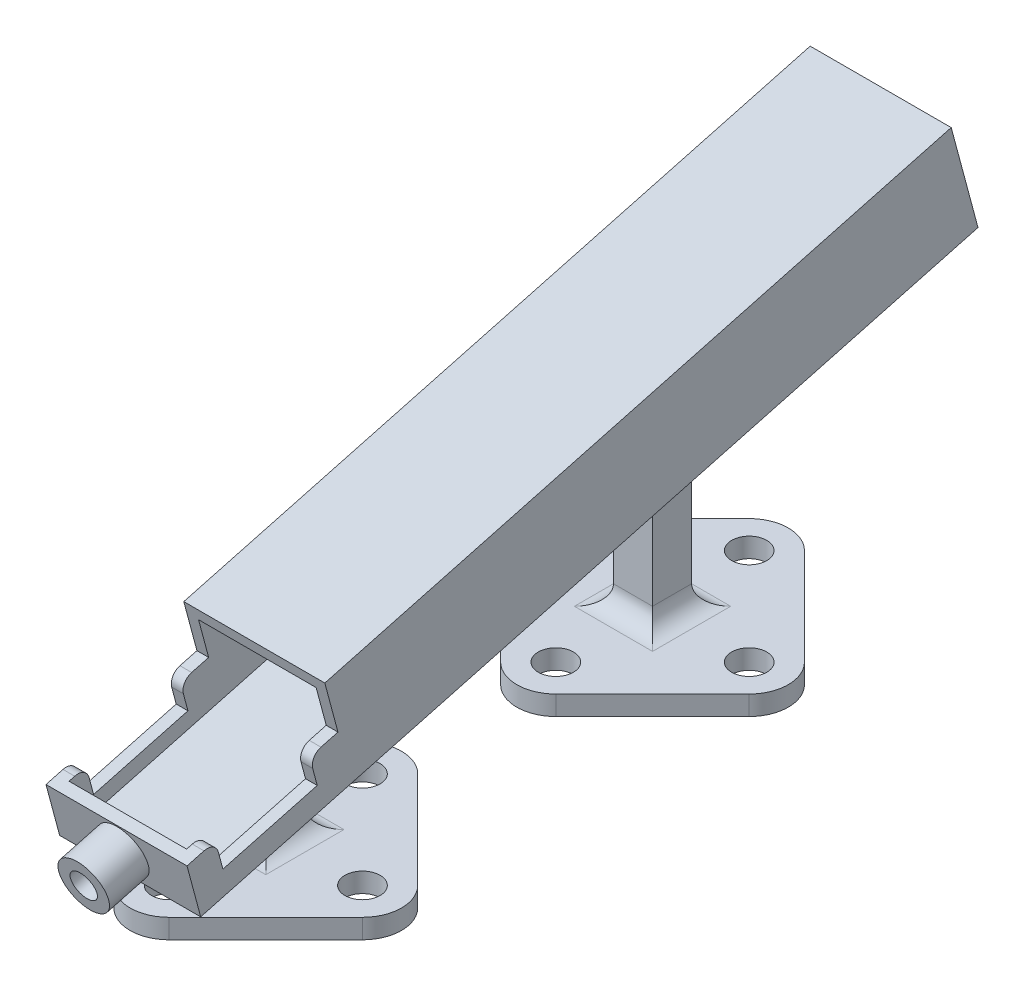
SolidWorks part; units mm, degrees
ref_plane "Front" through (0, 0, 0) normal (0, 0, 1) x (1, 0, 0)
ref_plane "Top" through (0, 0, 0) normal (0, 1, 0) x (1, 0, 0)
ref_plane "Right" through (0, 0, 0) normal (1, 0, 0) x (0, 0, -1)
ref_axis "Axis1" through (0, 55, 0) along (0, -1, 0)
ref_axis "Axis2" through (88.99, 0, 0) along (-1, 0, 0)
ref_axis "Axis3" through (0, 0, 55) along (0, 0, -1)
sketch "Sketch1" plane through (0, 0, 0) normal (0, 1, 0) x (1, 0, 0)
  line L0 (-24.75, 0) -> (0, 24.75) construction
  line L9 (-24.75, 0) -> (0, -24.75) construction
  line L11 (0, 24.75) -> (24.75, 0) construction
  line L12 (0, -24.75) -> (24.75, 0) construction
  line L13 (-24.75, 0) -> (24.75, 0) construction
  line L14 (0, 24.75) -> (0, -24.75) construction
  line L15 (-31.8211, 7.0711) -> (-7.0711, 31.8211)
  line L16 (7.0711, 31.8211) -> (31.8211, 7.0711)
  line L17 (7.0711, -31.8211) -> (31.8211, -7.0711)
  line L18 (-31.8211, -7.0711) -> (-7.0711, -31.8211)
  line L19 (0, -38.8921) -> (38.8921, 0) construction
  line L20 (-38.8921, 0) -> (0, -38.8921) construction
  line L21 (0, 38.8921) -> (38.8921, 0) construction
  line L22 (-38.8921, 0) -> (0, 38.8921) construction
  arc A4 (7.0711, -31.8211) -> (-7.0711, -31.8211) centre (0, -24.75) cw
  arc A5 (31.8211, 7.0711) -> (31.8211, -7.0711) centre (24.75, 0) cw
  arc A6 (-7.0711, 31.8211) -> (7.0711, 31.8211) centre (0, 24.75) cw
  arc A7 (-31.8211, 7.0711) -> (-31.8211, -7.0711) centre (-24.75, 0) ccw
  circle A8 centre (0, 24.75) radius 4.5
  circle A9 centre (24.75, 0) radius 4.5
  circle A10 centre (0, -24.75) radius 4.5
  circle A11 centre (-24.75, 0) radius 4.5
  point P1 (0, 0)
  dimension "D3" = 10
  dimension "D4" = 9
  dimension "D1" = 49.5
  dimension "D2" = 10
extrude "Boss-Extrude1" add sketch "Sketch1" along normal mid plane 5
ref_plane "Plane1" through (0, 0, 49.5) normal (0, 0, 1) x (1, 0, 0)
mirror "Mirror3" about plane through (0, 0, 49.5) normal (0, 0, 1) of bodies 101
sketch "Sketch2" plane through (0, 0, 0) normal (1, 0, 0) x (0, 0, -1)
  line L0 (-106.0711, 2.5) -> (-130.8211, 2.5) construction
  line L1 (-104, 2.5) -> (-94, 2.5)
  line L2 (-104, 2.5) -> (-104, 47.5)
  line L3 (-104, 47.5) -> (-94, 47.5)
  line L4 (-94, 2.5) -> (-94, 47.5)
  line L5 (-106.0711, -2.5) -> (-91.9289, -2.5) construction
  line L6 (-67.1789, -2.5) -> (-91.9289, -2.5) construction
  point P8 (-99, -2.5)
  point P9 (-99, 47.5)
  dimension "D1" = 10
  dimension "D2" = 50
extrude "Boss-Extrude2" add sketch "Sketch2" along normal mid plane 10 separate body
mirror "Mirror5" about plane through (0, 0, 49.5) normal (0, 0, 1) of bodies 103
sketch "Sketch3" plane through (0, 0, 0) normal (1, 0, 0) x (0, 0, -1)
  line L0 (-104, 17.5) -> (5, 46.7065)
  line L1 (-67.1789, -2.5) -> (-91.9289, -2.5) construction
  line L2 (-104, 47.5) -> (-104, 2.5) construction
  line L3 (-106.0711, 2.5) -> (-130.8211, 2.5) construction
  line L4 (5, 47.5) -> (5, 2.5) construction
  point P6 (-104, 17.5)
  dimension "D1" = 15
  dimension "D2" = 15
extrude "Cut-Extrude1" cut sketch "Sketch3" against normal through all both and the other way through all
sketch "Sketch4" plane through (0, 0, 0) normal (1, 0, 0) x (0, 0, -1)
  line L0 (-130.8211, 10.3133) -> (14.0678, 49.1362)
  line L1 (-130.8211, 10.3133) -> (-131.3387, 12.2452)
  line L2 (14.0678, 49.1362) -> (13.5502, 51.068)
  line L3 (-131.3387, 12.2452) -> (13.5502, 51.068)
  line L6 (-104, 17.5) -> (-94, 20.1795) construction
  dimension "D1" = 2
  dimension "D2" = 150
extrude "Boss-Extrude3" add sketch "Sketch4" along normal mid plane 30.1 separate body
combine bodies "Combine1" operation type add bodies to combine 102 106
combine bodies "Combine2" operation type add bodies to combine 107 101
fillet "Fillet1" radius 5 4 edges at (0, 2.5, 94) (-5, 2.5, 99) (0, 2.5, 104) (5, 2.5, 99)
fillet "Fillet2" radius 5 4 edges at (0, 2.5, 5) (0, 2.5, -5) (-5, 2.5, 0) (5, 2.5, 0)
sketch "Sketch5" plane through (0, 44.2596, 11.8593) normal (0, 0.9659, 0.2588) x (1, 0, 0)
  line L0 (15.05, -108.6442) -> (0, -108.6442) construction
  line L1 (15.05, 26.3058) -> (15.05, -123.6942) construction
  line L2 (0, -108.6442) -> (0, -123.6942) construction
  line L3 (15.05, -123.6942) -> (-15.05, -123.6942) construction
  line L4 (-11.83, -108.6442) -> (-15.05, -123.6942)
  line L5 (-15.05, -123.6942) -> (0, -123.6942)
  line L6 (0, -123.6942) -> (15.05, -123.6942)
  line L7 (15.05, -123.6942) -> (15.05, -108.6442)
  circle A0 centre (0, -108.6442) radius 8.73 construction
  circle A1 centre (0, -108.6442) radius 8.83
  circle A2 centre (0, -108.6442) radius 11.83
  dimension "D1" = 17.46
  dimension "D2" = 0.1
  dimension "D3" = 3
sketch "Sketch6" plane through (0, 44.2596, 11.8593) normal (0, 0.9659, 0.2588) x (1, 0, 0)
  line L4 (-15.05, 26.3058) -> (-15.05, -123.6942)
  line L5 (-15.05, -123.6942) -> (15.05, -123.6942)
  line L6 (15.05, -123.6942) -> (15.05, 26.3058)
  line L7 (15.05, 26.3058) -> (-15.05, 26.3058)
  line L8 (-15.05, 26.3058) -> (-15.05, -123.6942)
  line L9 (-15.05, -123.6942) -> (15.05, -123.6942)
  line L10 (15.05, -123.6942) -> (15.05, 26.3058)
  line L11 (15.05, 26.3058) -> (-15.05, 26.3058)
  line L16 (-18.05, 29.3058) -> (-18.05, -126.6942)
  line L17 (-18.05, -126.6942) -> (18.05, -126.6942)
  line L18 (18.05, -126.6942) -> (18.05, 29.3058)
  line L19 (18.05, 29.3058) -> (-18.05, 29.3058)
  line L20 (-18.05, 29.3058) -> (-18.05, -126.6942)
  line L21 (-18.05, -126.6942) -> (18.05, -126.6942)
  line L22 (18.05, -126.6942) -> (18.05, 29.3058)
  line L23 (18.05, 29.3058) -> (-18.05, 29.3058)
  dimension "D1" = 0
  dimension "D2" = 3
extrude "Boss-Extrude4" add sketch "Sketch6" against normal up to vertex (2 mm away) and the other way blind 16.5 up to point (15.05, 49.1362, -14.0678)
sketch "Sketch7" plane through (0, 60.1974, 16.1298) normal (0, 0.9659, 0.2588) x (1, 0, 0)
  line L0 (15.05, 26.3058) -> (15.05, -123.6942) construction
  line L1 (15.05, 26.3058) -> (15.05, -86.6942)
  line L3 (-15.05, 26.3058) -> (-15.05, -123.6942) construction
  line L4 (18.05, 29.3058) -> (-18.05, 29.3058)
  line L5 (-18.05, 29.3058) -> (-18.05, -126.6942)
  line L6 (-18.05, -126.6942) -> (18.05, -126.6942)
  line L7 (18.05, -126.6942) -> (18.05, 29.3058)
  line L8 (18.05, 29.3058) -> (-18.05, 29.3058)
  line L9 (-18.05, 29.3058) -> (-18.05, -86.6942)
  line L11 (18.05, -86.6942) -> (18.05, 29.3058)
  line L12 (15.05, 26.3058) -> (-15.05, 26.3058) construction
  line L14 (-15.05, 26.3058) -> (-15.05, -86.6942)
  line L15 (15.05, 26.3058) -> (-15.05, 26.3058)
  line L16 (18.05, -86.6942) -> (15.05, -86.6942)
  line L17 (-15.05, -86.6942) -> (-18.05, -86.6942)
  line L18 (-18.05, -126.6942) -> (18.05, -126.6942) construction
  dimension "D2" = 40
  dimension "D1" = 0
extrude "Boss-Extrude5" add sketch "Sketch7" along normal blind 5
sketch "Sketch8" plane through (0, 65.027, 17.4239) normal (0, 0.9659, 0.2588) x (1, 0, 0)
  line L0 (-18.05, 29.3058) -> (-18.05, -86.6942) construction
  line L1 (-18.05, -86.6942) -> (18.05, -86.6942)
  line L2 (-18.05, -86.6942) -> (-18.05, 29.3058)
  line L3 (-18.05, 29.3058) -> (18.05, 29.3058)
  line L4 (18.05, -86.6942) -> (18.05, 29.3058)
extrude "Boss-Extrude6" add sketch "Sketch8" along normal blind 3
sketch "Sketch10" plane through (0, 6.8085, -25.4095) normal (0, -0.2588, 0.9659) x (1, 0, 0)
  line L4 (-15.05, 45.8209) -> (15.05, 45.8209)
  line L5 (15.05, 45.8209) -> (15.05, 67.3209)
  line L6 (15.05, 67.3209) -> (-15.05, 67.3209)
  line L7 (-15.05, 67.3209) -> (-15.05, 45.8209)
  line L8 (-15.05, 45.8209) -> (15.05, 45.8209)
  line L9 (15.05, 45.8209) -> (15.05, 67.3209)
  line L10 (15.05, 67.3209) -> (-15.05, 67.3209)
  line L11 (-15.05, 67.3209) -> (-15.05, 45.8209)
  dimension "D1" = 0
extrude "Cut-Extrude2" cut sketch "Sketch10" against normal up to next
sketch "Sketch11" plane through (0, 60.1974, 16.1298) normal (0, 0.9659, 0.2588) x (1, 0, 0)
  line L1 (-18.05, -126.6942) -> (18.05, -126.6942)
  line L2 (-18.05, -126.6942) -> (-18.05, -86.6942)
  line L3 (-18.05, -86.6942) -> (18.05, -86.6942)
  line L4 (18.05, -126.6942) -> (18.05, -86.6942)
extrude "Cut-Extrude3" cut sketch "Sketch11" against normal blind 5
sketch "Sketch12" plane through (0, 55.3677, 14.8357) normal (0, 0.9659, 0.2588) x (1, 0, 0)
  line L0 (-18.05, -86.6942) -> (-18.05, -126.6942) construction
  line L1 (-18.05, -119.1942) -> (-15.05, -119.1942)
  line L2 (-18.05, -119.1942) -> (-18.05, -94.1942)
  line L3 (-18.05, -94.1942) -> (-15.05, -94.1942)
  line L4 (-15.05, -119.1942) -> (-15.05, -94.1942)
  line L5 (-15.05, 29.3058) -> (-15.05, -123.6942) construction
  line L6 (-18.05, -126.6942) -> (18.05, -126.6942) construction
  line L7 (0, -123.6942) -> (0, -86.6942) construction
  line L8 (15.05, -123.6942) -> (-15.05, -123.6942) construction
  line L9 (-18.05, -86.6942) -> (18.05, -86.6942) construction
  line L10 (15.05, -119.1942) -> (15.05, -94.1942)
  line L11 (18.05, -94.1942) -> (15.05, -94.1942)
  line L12 (18.05, -119.1942) -> (18.05, -94.1942)
  line L13 (18.05, -119.1942) -> (15.05, -119.1942)
  dimension "D1" = 25
  dimension "D2" = 7.5
extrude "Cut-Extrude4" cut sketch "Sketch12" against normal blind 7.5
sketch "Sketch13" plane through (0, -32.7909, 122.3772) normal (0, -0.2588, 0.9659) x (1, 0, 0)
  line L0 (-18.05, 57.3209) -> (-18.05, 43.8209) construction
  line L1 (-18.05, 57.3209) -> (18.05, 57.3209) construction
  circle A0 centre (0, 50.5709) radius 3.4
  point P5 (-18.05, 50.5709)
  point P8 (0, 57.3209)
  dimension "D1" = 6.8
extrude "Cut-Extrude5" cut sketch "Sketch13" against normal up to next
sketch "Sketch14" plane through (0, -32.7909, 122.3772) normal (0, -0.2588, 0.9659) x (1, 0, 0)
  circle A0 centre (0, 50.5709) radius 3.4 construction
  circle A1 centre (0, 50.5709) radius 3.4
  circle A2 centre (0, 50.5709) radius 6.4
  dimension "D1" = 3
extrude "Boss-Extrude7" add sketch "Sketch14" along normal blind 10.5
fillet "Fillet3" radius 3 4 edges at (-16.55, 24.518, 129.9685) (16.55, 24.518, 129.9685) (16.55, 30.9885, 105.8203) (-16.55, 30.9885, 105.8203)
sketch "Sketch15" plane through (0, 7.5849, -28.3073) normal (0, 0.2588, -0.9659) x (-1, 0, 0)
  line L5 (15.05, 67.3209) -> (-15.05, 67.3209)
  line L6 (15.05, 45.8209) -> (15.05, 67.3209)
  line L7 (-15.05, 45.8209) -> (15.05, 45.8209)
  line L8 (-15.05, 67.3209) -> (-15.05, 45.8209)
  line L9 (15.05, 67.3209) -> (-15.05, 67.3209)
  line L10 (15.05, 45.8209) -> (15.05, 67.3209)
  line L11 (-15.05, 45.8209) -> (15.05, 45.8209)
  line L12 (-15.05, 67.3209) -> (-15.05, 45.8209)
  line L13 (-18.05, 70.3209) -> (-18.05, 43.8209)
  line L14 (-18.05, 43.8209) -> (18.05, 43.8209)
  line L15 (18.05, 43.8209) -> (18.05, 70.3209)
  line L16 (18.05, 70.3209) -> (-18.05, 70.3209)
  line L17 (-18.05, 70.3209) -> (-18.05, 43.8209)
  line L18 (-18.05, 43.8209) -> (18.05, 43.8209)
  line L19 (18.05, 43.8209) -> (18.05, 70.3209)
  line L20 (18.05, 70.3209) -> (-18.05, 70.3209)
  dimension "D1" = 0
  dimension "D2" = 0
extrude "Boss-Extrude8" add sketch "Sketch15" along normal blind 50
